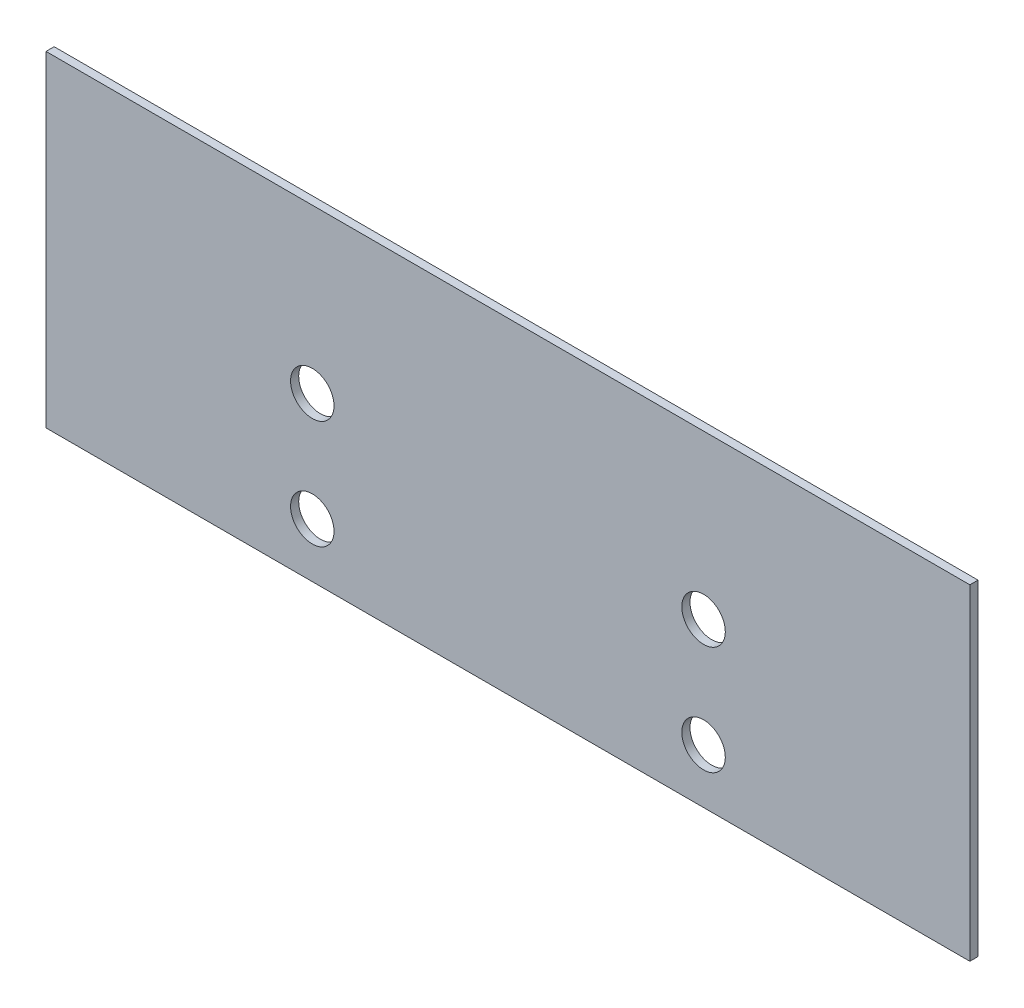
SolidWorks part; units mm, degrees
material "AISI 316 Chapa de acero inoxidable (SS)"
ref_plane "Alzado" through (0, 0, 0) normal (0, 0, 1) x (1, 0, 0)
ref_plane "Planta" through (0, 0, 0) normal (0, 1, 0) x (1, 0, 0)
ref_plane "Vista lateral" through (0, 0, 0) normal (1, 0, 0) x (0, 0, -1)
sketch "Croquis1" plane through (0, 0, 0) normal (0, 0, 1) x (1, 0, 0)
  line L1 (-85, -30) -> (85, -30)
  line L2 (-85, -30) -> (-85, 30)
  line L3 (-85, 30) -> (85, 30)
  line L4 (85, -30) -> (85, 30)
  line L5 (-85, -30) -> (85, 30) construction
  line L6 (-85, 30) -> (85, -30) construction
  point P0 (0, 0)
  dimension "D1" = 60
  dimension "D2" = 170
extrude "Saliente-Extruir1" add sketch "Croquis1" along normal blind 1.5
sketch "Croquis2" plane through (0, 0, 1.5) normal (0, 0, 1) x (1, 0, 0)
  circle A0 centre (-36, -20) radius 4 construction
  circle A1 centre (-36, 0) radius 4 construction
  circle A2 centre (36, -20) radius 4 construction
  circle A3 centre (36, 0) radius 4 construction
  circle A4 centre (-36, -20) radius 4
  circle A5 centre (-36, 0) radius 4
  circle A6 centre (36, -20) radius 4
  circle A7 centre (36, 0) radius 4
extrude "Cortar-Extruir1" cut sketch "Croquis2" against normal up to surface (1.5 mm away) up to face at (0, 0, 0)
